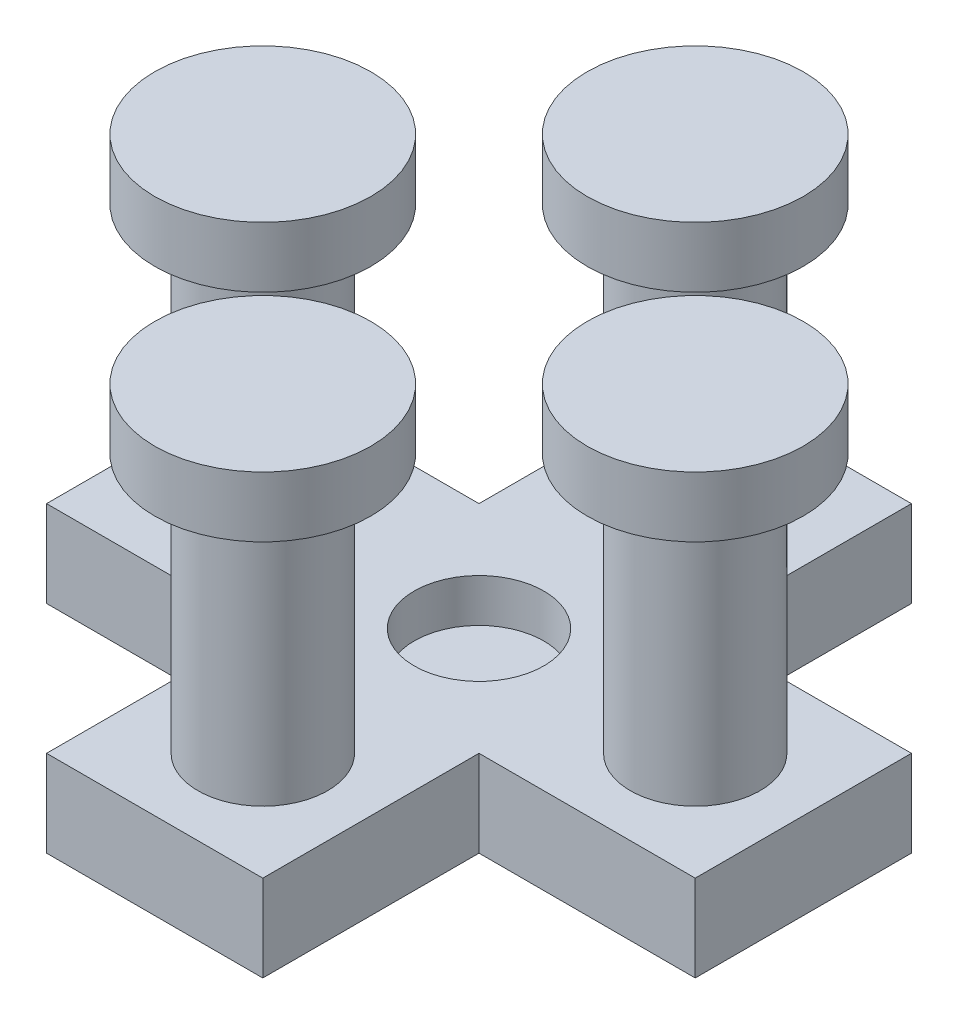
SolidWorks part; units mm, degrees
ref_plane "Front Plane" through (0, 0, 0) normal (0, 0, 1) x (1, 0, 0)
ref_plane "Top Plane" through (0, 0, 0) normal (0, 1, 0) x (1, 0, 0)
ref_plane "Right Plane" through (0, 0, 0) normal (1, 0, 0) x (0, 0, -1)
sketch "Sketch1" plane through (0, 0, 0) normal (0, 1, 0) x (1, 0, 0)
  line L0 (-8.3487, -10.4521) -> (-8.3487, -4.1021)
  line L1 (-8.3487, -4.1021) -> (-1.9987, -4.1021)
  line L2 (-1.9987, -4.1021) -> (-1.9987, -10.4521)
  line L3 (-1.9987, -10.4521) -> (4.3513, -10.4521)
  line L4 (4.3513, -10.4521) -> (4.3513, -16.8021)
  line L5 (4.3513, -16.8021) -> (-1.9987, -16.8021)
  line L6 (-1.9987, -16.8021) -> (-1.9987, -23.1521)
  line L7 (-1.9987, -23.1521) -> (-8.3487, -23.1521)
  line L8 (-8.3487, -23.1521) -> (-8.3487, -16.8021)
  line L9 (-8.3487, -16.8021) -> (-14.6987, -16.8021)
  line L10 (-14.6987, -16.8021) -> (-14.6987, -10.4521)
  line L11 (-14.6987, -10.4521) -> (-8.3487, -10.4521)
  dimension "D1" = 6.35
  dimension "D2" = 6.35
  dimension "D3" = 6.35
  dimension "D4" = 6.35
  dimension "D5" = 6.35
  dimension "D6" = 6.35
  dimension "D7" = 6.35
  dimension "D8" = 6.35
  dimension "D9" = 6.35
  dimension "D10" = 6.35
extrude "body" add sketch "Sketch1" along normal blind 2.54
sketch "Sketch2" plane through (0, 2.54, 0) normal (0, 1, 0) x (1, 0, 0)
  line L0 (-8.3487, -10.4521) -> (-14.6987, -10.4521) construction
  line L1 (-1.9987, -23.1521) -> (-1.9987, -16.8021) construction
  line L2 (-1.9987, -16.8021) -> (4.3513, -16.8021) construction
  line L3 (-1.9987, -10.4521) -> (-1.9987, -4.1021) construction
  line L4 (-1.9987, -4.1021) -> (-8.3487, -4.1021) construction
  line L5 (-14.6987, -10.4521) -> (-14.6987, -16.8021) construction
  line L6 (-8.3487, -23.1521) -> (-1.9987, -23.1521) construction
  line L7 (4.3513, -16.8021) -> (4.3513, -10.4521) construction
  circle A0 centre (-5.1737, -7.2771) radius 1.905
  circle A1 centre (1.1763, -13.6271) radius 1.905
  circle A2 centre (-5.1737, -19.9771) radius 1.905
  circle A3 centre (-11.5237, -13.6271) radius 1.905
  dimension "D1" = 3.81
  dimension "D2" = 3.81
  dimension "D3" = 3.81
  dimension "D4" = 3.81
  dimension "D5" = 3.175
  dimension "D6" = 3.175
  dimension "D7" = 3.175
  dimension "D8" = 3.175
  dimension "D9" = 3.175
  dimension "D10" = 3.175
  dimension "D11" = 3.175
  dimension "D12" = 3.175
extrude "flag" add sketch "Sketch2" along normal blind 7.62
ref_point "centre of flag top"
ref_point "centre 2"
ref_point "centre 3"
ref_point "centre 4"
ref_plane "plane o' feet" through (0, 10.16, 0) normal (0, 1, 0) x (1, 0, 0)
sketch "Sketch3" plane through (0, 10.16, 0) normal (0, 1, 0) x (1, 0, 0)
  circle A0 centre (-5.1737, -7.2771) radius 3.175
  circle A1 centre (-11.5237, -13.6271) radius 3.175
  circle A2 centre (-5.1737, -19.9771) radius 3.175
  circle A3 centre (1.1763, -13.6271) radius 3.175
  dimension "D1" = 6.35
  dimension "D2" = 6.35
  dimension "D3" = 6.35
  dimension "D4" = 6.35
extrude "feet" add sketch "Sketch3" along normal blind 1.778
sketch "Sketch4" plane through (0, 2.54, 0) normal (0, 1, 0) x (1, 0, 0)
  line L0 (-8.3487, -23.1521) -> (-1.9987, -23.1521) construction
  line L3 (-1.9987, -4.1021) -> (-8.3487, -4.1021) construction
  circle A0 centre (-5.1737, -13.6271) radius 1.905
  point P10 (-5.1737, -4.1021)
  point P14 (-5.1737, -23.1521)
  dimension "D1" = 3.81
  dimension "D2" = 9.525
  dimension "D3" = 0
extrude "spring hole" cut sketch "Sketch4" against normal blind 1.27
ref_point "centre of flag base"
